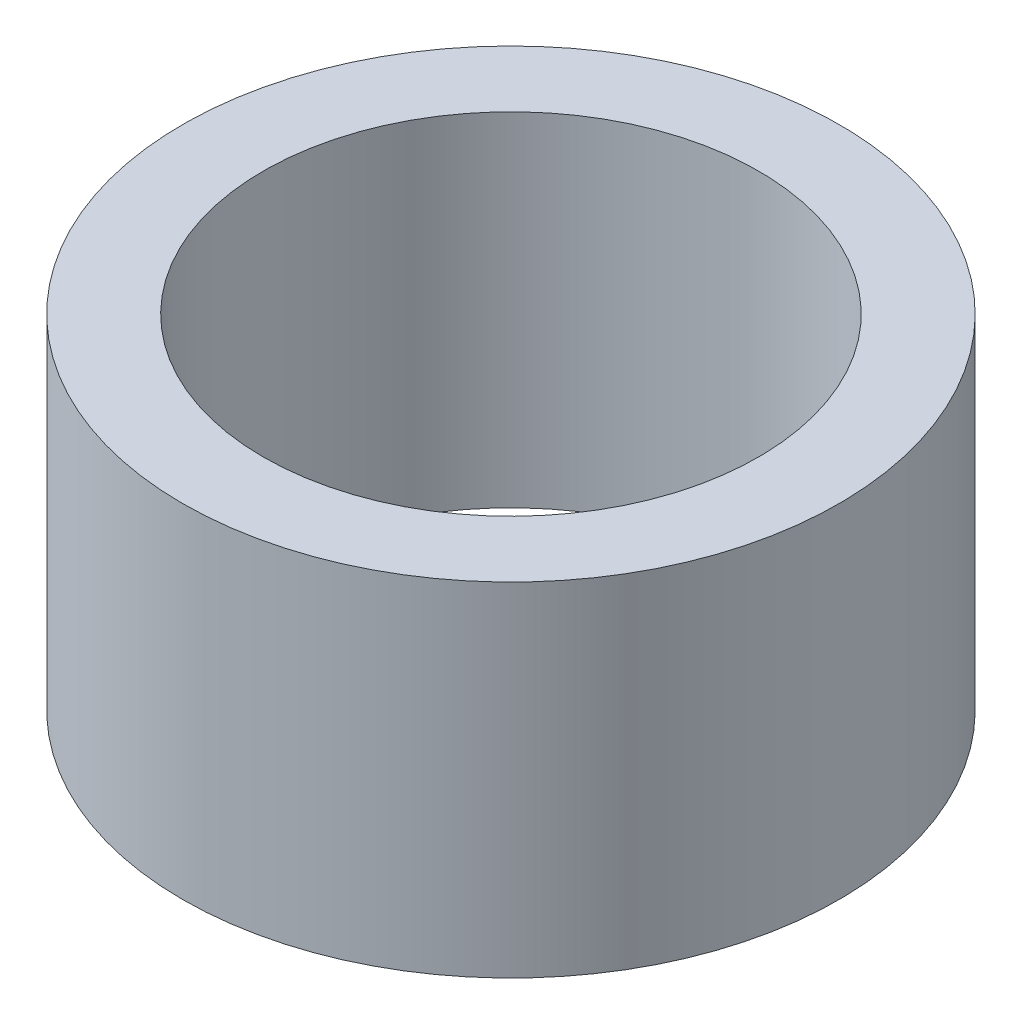
SolidWorks part; units mm, degrees
ref_plane "Front Plane" through (0, 0, 0) normal (0, 0, 1) x (1, 0, 0)
ref_plane "Top Plane" through (0, 0, 0) normal (0, 1, 0) x (1, 0, 0)
ref_plane "Right Plane" through (0, 0, 0) normal (1, 0, 0) x (0, 0, -1)
sketch "Sketch1" plane through (0, 0, 0) normal (0, 1, 0) x (1, 0, 0)
  circle A0 centre (0, 0) radius 35
  dimension "SLEEVE_OD" = 70
extrude "Boss-Extrude1" add sketch "Sketch1" along normal blind 36.565
sketch "Sketch2" plane through (0, 0, 0) normal (0, 1, 0) x (1, 0, 0)
  circle A0 centre (0, 0) radius 26.4085
  dimension "BORE_D" = 52.817
extrude "Cut-Extrude1" cut sketch "Sketch2" along normal through all
chamfer "Chamfer1" distance 3.0593 angle 68.151 rebuild error yes
